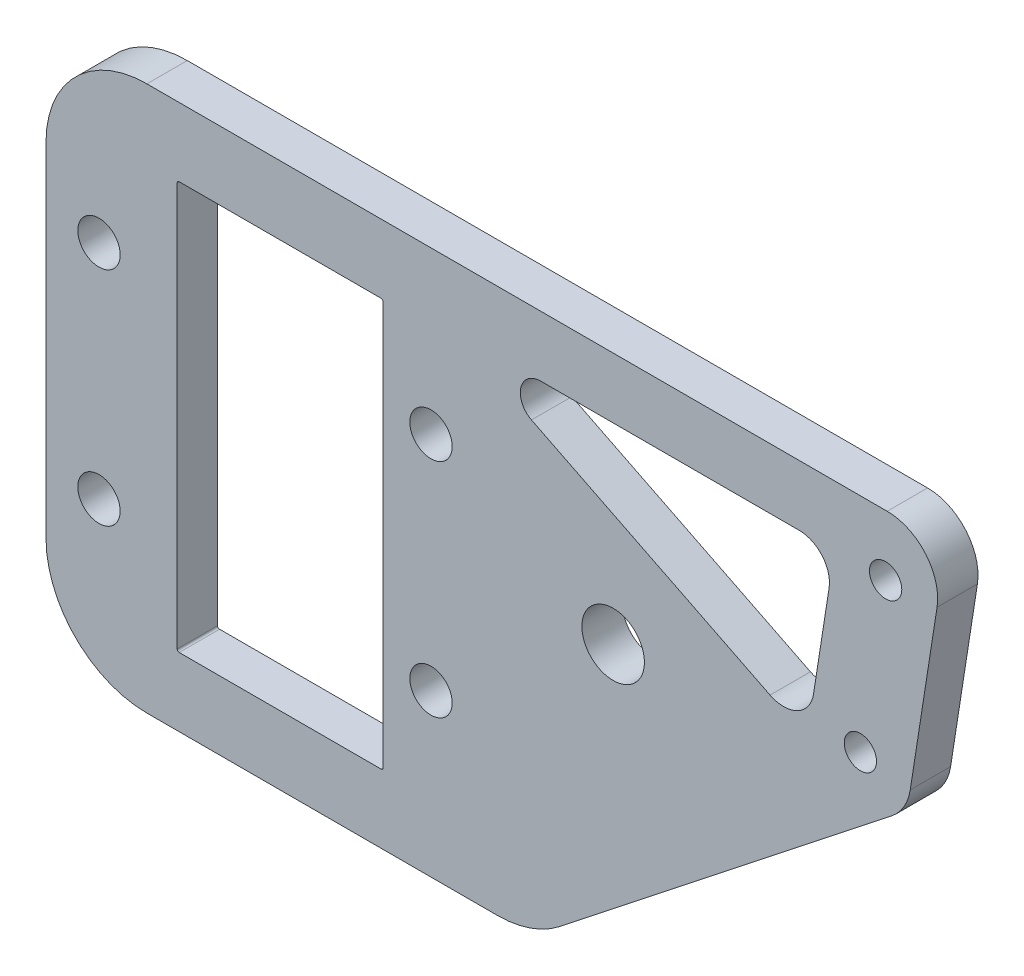
SolidWorks part; units mm, degrees
ref_plane "前视基准面" through (0, 0, 0) normal (0, 0, 1) x (1, 0, 0)
ref_plane "上视基准面" through (0, 0, 0) normal (0, 1, 0) x (1, 0, 0)
ref_plane "右视基准面" through (0, 0, 0) normal (1, 0, 0) x (0, 0, -1)
sketch "草图1" plane through (0, 0, 0) normal (0, 0, 1) x (1, 0, 0)
  line L0 (-10.2, 20.2) -> (10.2, 20.2)
  line L1 (-10, -20) -> (10, -20) construction
  line L2 (-10, -20) -> (-10, 20) construction
  line L3 (-10, 20) -> (10, 20) construction
  line L4 (10, -20) -> (10, 20) construction
  line L5 (-10, -20) -> (10, 20) construction
  line L6 (-10, 20) -> (10, -20) construction
  line L7 (10.2, -20.2) -> (10.2, 20.2)
  line L8 (-10.2, -20.2) -> (10.2, -20.2)
  line L9 (-10.2, -20.2) -> (-10.2, 20.2)
  line L10 (-13.2, 27) -> (60.1562, 27)
  line L11 (33, 25) -> (33, -25) construction
  line L12 (21.5311, -27) -> (-13.2, -27)
  line L13 (-23.2, -17) -> (-23.2, 17)
  line L15 (27.7237, -24.8519) -> (60.5963, 1.0741)
  line L16 (62.4401, 4.2281) -> (65.0963, 21.2281)
  circle A0 centre (33, 2) radius 3.1
  arc A1 (-13.2, -27) -> (-23.2, -17) centre (-13.2, -17) cw
  arc A2 (-13.2, 27) -> (-23.2, 17) centre (-13.2, 17) ccw
  circle A6 centre (33, 2) radius 12.5 construction
  circle A9 centre (60, 21) radius 1.6
  circle A10 centre (57.5, 5) radius 1.6
  arc A12 (60.5963, 1.0741) -> (62.4401, 4.2281) centre (57.5, 5) ccw
  arc A13 (21.5311, -27) -> (27.7237, -24.8519) centre (21.5311, -17) ccw
  arc A14 (65.0963, 21.2281) -> (60.1562, 27) centre (60.1562, 22) ccw
  point P0 (0, 0)
  point P32 (25, -27)
  dimension "D8" = 6.2
  dimension "D10" = 10
  dimension "D11" = 3.2
  dimension "D12" = 19
  dimension "D13" = 25
  dimension "D9" = 25
  dimension "D14" = 27
  dimension "D15" = 3.2
  dimension "D18" = 10
  dimension "D20" = 10
  dimension "D21" = 5
  dimension "D1" = 40
  dimension "D2" = 20
  dimension "D3" = 0.2
  dimension "D4" = 7
  dimension "D5" = 7
  dimension "D6" = 13
  dimension "D7" = 43
  dimension "D16" = 3
  dimension "D17" = 24.5
  dimension "D19" = 25
  dimension "D22" = 5
extrude "凸台-拉伸1" add sketch "草图1" along normal blind 4
fillet "圆角1" radius 0.2 4 edges at (10.2, -20.2, 2) (-10.2, -20.2, 2) (-10.2, 20.2, 2) (10.2, 20.2, 2)
sketch "草图2" plane through (0, 0, 4) normal (0, 0, 1) x (1, 0, 0)
  line L0 (14.95, 11) -> (14.95, -11) construction
  line L1 (9.95, 20.25) -> (9.95, -49979.75) construction
  line L2 (0, 0) -> (50000, 0) construction
  line L3 (10.2, -20) -> (10.2, 20) construction
  line L4 (0, 0.6321) -> (0, 50000.6321) construction
  line L5 (-17.95, 11) -> (-17.95, -11) construction
  circle A0 centre (14.95, 11) radius 2.1
  circle A4 centre (14.95, -11) radius 2.1
  circle A5 centre (-17.95, -11) radius 2.1
  circle A6 centre (-17.95, 11) radius 2.1
  point P17 (0, 0)
  dimension "D1" = 4.2
  dimension "D2" = 22
  dimension "D3" = 17.95
  dimension "D6" = 4.2
  dimension "D7" = 4.2
  dimension "D8" = 17.95
  dimension "D4" = 0.25
  dimension "D5" = 5
extrude "切除-拉伸1" cut sketch "草图2" against normal blind 4
sketch "草图3" plane through (0, 0, 4) normal (0, 0, 1) x (1, 0, 0)
  line L0 (25.798, 21) -> (51.4342, 21)
  line L1 (54.3982, 17.5369) -> (52.8522, 7.6426)
  line L2 (48.5495, 5.4209) -> (24.9056, 17.2102)
  line L3 (60.1562, 27) -> (-13.2, 27) construction
  line L4 (14.95, 11) -> (33, 2) construction
  line L5 (57.5, 5) -> (60, 21) construction
  line L6 (62.4401, 4.2281) -> (65.0963, 21.2281) construction
  arc A0 (54.3982, 17.5369) -> (51.4342, 21) centre (51.4342, 18) ccw
  arc A1 (24.9056, 17.2102) -> (25.798, 21) centre (25.798, 19) cw
  arc A2 (48.5495, 5.4209) -> (52.8522, 7.6426) centre (49.8882, 8.1057) ccw
  dimension "3" = 3
  dimension "D2" = 2
  dimension "D3" = 3
  dimension "D1" = 6
  dimension "D4" = 10
  dimension "D5" = 10
extrude "切除-拉伸2" cut sketch "草图3" against normal blind 10
equation "\"4。2\"=3.2"
equation "\"6。2\"=6.5866"
equation "\"3。2\"=6.2"
equation "\"12。5\"=10"
